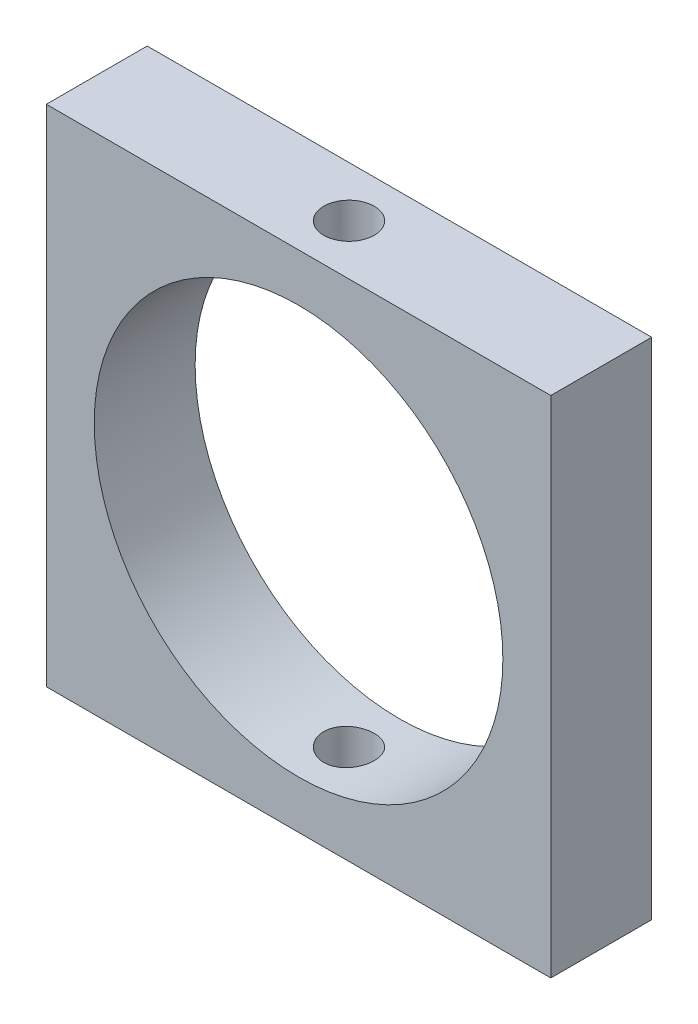
SolidWorks part; units mm, degrees
material "1060 Alloy"
ref_plane "Front Plane" through (0, 0, 0) normal (0, 0, 1) x (1, 0, 0)
ref_plane "Top Plane" through (0, 0, 0) normal (0, 1, 0) x (1, 0, 0)
ref_plane "Right Plane" through (0, 0, 0) normal (1, 0, 0) x (0, 0, -1)
sketch "Sketch1" plane through (0, 0, 0) normal (0, 0, 1) x (1, 0, 0)
  line L1 (-10, -10) -> (10, -10)
  line L2 (-10, -10) -> (-10, 10)
  line L3 (-10, 10) -> (10, 10)
  line L4 (10, -10) -> (10, 10)
  line L5 (-10, -10) -> (10, 10) construction
  line L6 (-10, 10) -> (10, -10) construction
  circle A0 centre (0, 0) radius 8.1
  point P0 (0, 0)
extrude "Boss-Extrude1" add sketch "Sketch1" along normal blind 4
sketch "Sketch3" plane through (0, 10, 0) normal (0, 1, 0) x (1, 0, 0)
  circle A0 centre (0, -2) radius 1
extrude "Cut-Extrude1" cut sketch "Sketch3" against normal blind 20
